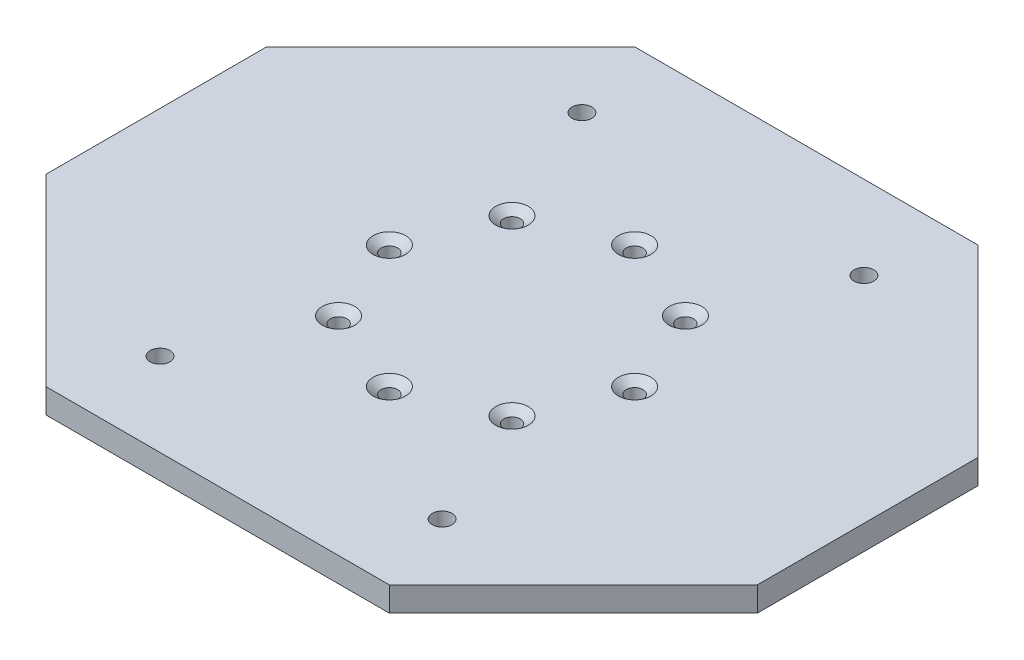
SolidWorks part; units mm, degrees
material "6061-T6 (SS)"
ref_plane "Front Plane" through (0, 0, 0) normal (0, 0, 1) x (1, 0, 0)
ref_plane "Top Plane" through (0, 0, 0) normal (0, 1, 0) x (1, 0, 0)
ref_plane "Right Plane" through (0, 0, 0) normal (1, 0, 0) x (0, 0, -1)
sketch "Sketch1" plane through (0, 0, 0) normal (0, 1, 0) x (1, 0, 0)
  line L0 (-92.075, 28.575) -> (-44.45, 76.2)
  line L1 (-44.45, -76.2) -> (44.45, -76.2)
  line L2 (-92.075, -28.575) -> (-92.075, 28.575)
  line L3 (-44.45, 76.2) -> (44.45, 76.2)
  line L4 (92.075, -28.575) -> (92.075, 28.575)
  line L7 (44.45, 76.2) -> (92.075, 28.575)
  line L8 (92.075, -28.575) -> (44.45, -76.2)
  line L9 (-92.075, -28.575) -> (-44.45, -76.2)
  line L11 (-38.1, 73.025) -> (38.1, 73.025) construction
  line L12 (-38.1, 73.025) -> (-38.1, 47.625) construction
  line L13 (-38.1, 47.625) -> (38.1, 47.625) construction
  line L14 (38.1, 73.025) -> (38.1, 47.625) construction
  line L15 (-38.1, 73.025) -> (38.1, 47.625) construction
  line L16 (-38.1, 47.625) -> (38.1, 73.025) construction
  line L17 (-44.45, 75.565) -> (44.45, 75.565) construction
  line L18 (-44.45, 75.565) -> (-44.45, 45.085) construction
  line L19 (-44.45, 45.085) -> (44.45, 45.085) construction
  line L20 (44.45, 75.565) -> (44.45, 45.085) construction
  line L21 (-44.45, 75.565) -> (44.45, 45.085) construction
  line L22 (-44.45, 45.085) -> (44.45, 75.565) construction
  circle A0 centre (0, 0) radius 38.1 construction
  circle A1 centre (0, 0) radius 41.275 construction
  point P0 (0, 0)
  point P17 (0, 60.325)
  point P22 (0, 60.325)
  point P27 (-92.075, 0)
  point P28 (0, 76.2)
  dimension "D4" = 76.2
  dimension "D5" = 82.55
  dimension "D2" = 135
  dimension "D3" = 88.9
  dimension "D6" = 2.54
  dimension "D7" = 25.4
  dimension "D8" = 76.2
  dimension "D9" = 88.9
  dimension "D10" = 6.35
  dimension "D11" = 152.4
  dimension "D12" = 184.15
extrude "Boss-Extrude1" add sketch "Sketch1" along normal blind 6.35
hole_wizard "#7 (0.201) Diameter Hole1" positions "Sketch3" profile "Sketch2" hole size "#7" standard "ANSI Inch" end condition through all
sketch "Sketch3" plane through (0, 6.35, 0) normal (0, 1, 0) x (-1, 0, 0)
  line L0 (-36.5125, -54.61) -> (0, 0) construction
  line L1 (0, 0) -> (36.5125, -54.61) construction
  line L5 (-873.478, -47.625) -> (49126.522, -47.625) construction
  point P0 (36.5125, -54.61)
  point P1 (-36.5125, -54.61)
  dimension "D1" = 73.025
  dimension "D2" = 47.625
  dimension "D3" = 6.985
sketch "Sketch2" plane through (-36.5125, 6.35, -54.61) normal (1, 0, 0) x (0, 0, 1)
  line L0 (0, 0) -> (0, 6.35)
  line L1 (0, 6.35) -> (2.5527, 6.35)
  line L2 (2.5527, 6.35) -> (2.5527, 0)
  line L5 (2.5527, 0) -> (0, 0)
  line L11 (0, -6.35) -> (0, 107.95) construction
  dimension "Thru Hole Dia." = 5.1054
  dimension "Thru Hole Depth" = 6.35
ref_axis "Axis1" through (0, 0, 0) along (0, 1, 0)
pattern_circular "CirPattern1" count 2 over 360 about axis through (0, 0, 0) along (0, 1, 0) of "#7 (0.201) Diameter Hole1"
hole_wizard "CSK for #8 Flat Head Machine Screw (100)1" positions "Sketch5" profile "Sketch4" countersink size "#8" standard "Ansi Inch" end condition through all
sketch "Sketch5" plane through (0, 6.35, 0) normal (0, 1, 0) x (-1, 0, 0)
  point P0 (0, 31.75)
  dimension "D1" = 31.75
sketch "Sketch4" plane through (0, 6.35, 31.75) normal (1, 0, 0) x (0, 0, 1)
  line L0 (0, 0) -> (0, 6.35)
  line L1 (0, 6.35) -> (2.1526, 6.35)
  line L2 (2.1526, 6.35) -> (2.1526, 1.7317)
  line L3 (2.1526, 1.7317) -> (4.2164, 0)
  line L5 (4.2164, 0) -> (0, 0)
  line L6 (-2.1526, 1.7317) -> (-4.2164, 0) construction
  line L11 (0, -6.35) -> (0, 107.95) construction
  dimension "Thru Hole Dia." = 4.3053
  dimension "Thru Hole Depth" = 6.35
  dimension "Near C'Sink Dia." = 8.4328
  dimension "Near C'Sink Angle" = 100
pattern_circular "CirPattern2" count 8 over 360 about axis through (0, 0, 0) along (0, 1, 0) of "CSK for #8 Flat Head Machine Screw (100)1"
